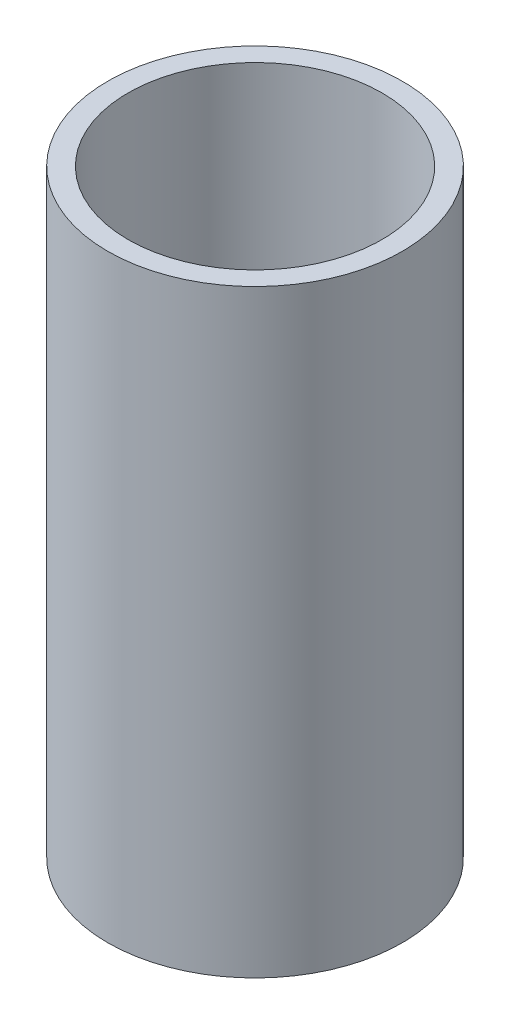
SolidWorks part; units mm, degrees
ref_plane "Front Plane" through (0, 0, 0) normal (0, 0, 1) x (1, 0, 0)
ref_plane "Top Plane" through (0, 0, 0) normal (0, 1, 0) x (1, 0, 0)
ref_plane "Right Plane" through (0, 0, 0) normal (1, 0, 0) x (0, 0, -1)
sketch "Sketch1" plane through (0, 0, 0) normal (0, 1, 0) x (1, 0, 0)
  circle A0 centre (0, 0) radius 32.5
  dimension "SLEEVE_OD" = 65
extrude "Boss-Extrude1" add sketch "Sketch1" along normal blind 132.0798
sketch "Sketch2" plane through (0, 0, 0) normal (0, 1, 0) x (1, 0, 0)
  circle A0 centre (0, 0) radius 28.0183
  dimension "BORE_D" = 56.0367
extrude "Cut-Extrude1" cut sketch "Sketch2" along normal through all
chamfer "Chamfer1" distance 3.0616 angle 30 rebuild error yes
